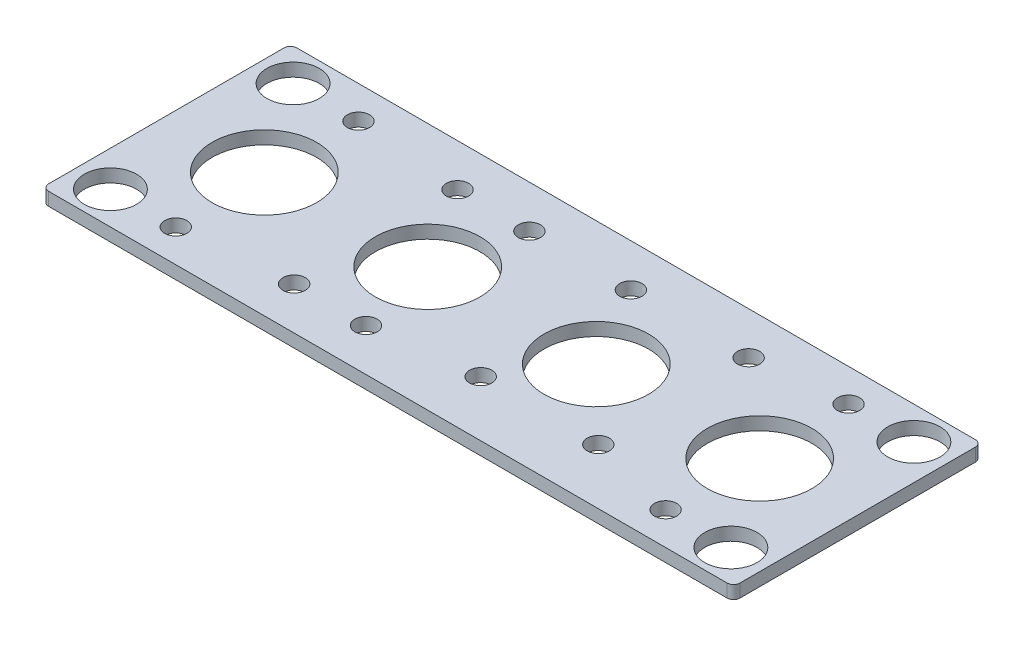
SolidWorks part; units mm, degrees
ref_plane "Front Plane" through (0, 0, 0) normal (0, 0, 1) x (1, 0, 0)
ref_plane "Top Plane" through (0, 0, 0) normal (0, 1, 0) x (1, 0, 0)
ref_plane "Right Plane" through (0, 0, 0) normal (1, 0, 0) x (0, 0, -1)
sketch "Sketch1" plane through (0, 0, 0) normal (0, 1, 0) x (1, 0, 0)
  line L1 (-52.9, 19) -> (52.9, 19)
  line L2 (-52.9, 19) -> (-52.9, -19)
  line L3 (-52.9, -19) -> (52.9, -19)
  line L4 (52.9, 19) -> (52.9, -19)
  circle A0 centre (-47.5, 14) radius 4
  circle A1 centre (-47.4521, -14) radius 4
  circle A2 centre (47.5, 14) radius 4
  circle A3 centre (47.5, -14) radius 4
  circle A4 centre (-20.8388, 12.5) radius 1.7
  circle A5 centre (-20.8388, -12.5) radius 1.7
  circle A6 centre (-9.8388, 12.5) radius 1.7
  circle A7 centre (-9.8388, -12.5) radius 1.7
  circle A8 centre (5.7083, 12.4823) radius 1.7
  circle A9 centre (5.7083, -10.5) radius 1.7
  circle A10 centre (23.7083, 12.5) radius 1.7
  circle A11 centre (23.7083, -10.5) radius 1.7
  circle A12 centre (-37.5, 14) radius 1.7
  circle A13 centre (-37.4521, -14) radius 1.7
  circle A14 centre (37.5, 14) radius 1.7
  circle A15 centre (37.5, -14) radius 1.7
  circle A16 centre (-37.9, 0) radius 8
  circle A17 centre (-12.9, 0) radius 8
  circle A19 centre (37.9, 0) radius 8
  circle A20 centre (12.9, 0) radius 8
  dimension "D3" = 28
  dimension "D4" = 95
  dimension "D5" = 105.8
  dimension "D7" = 11
  dimension "D10" = 6.5
  dimension "D13" = 10
  dimension "D18" = 75
  dimension "D19" = 52.9
  dimension "D25" = 15
  dimension "D24" = 15
  dimension "D26" = 25
  dimension "D1" = 5
  dimension "D2" = 5
  dimension "D6" = 5.4
  dimension "D8" = 25
  dimension "D9" = 6.5
  dimension "D11" = 23
  dimension "D12" = 18
  dimension "D14" = 10
  dimension "D15" = 10
  dimension "D16" = 10
  dimension "D17" = 28
  dimension "D20" = 19
  dimension "D21" = 0
  dimension "D22" = 25
  dimension "D23" = 11
  dimension "D27" = 25
extrude "Boss-Extrude3" add sketch "Sketch1" along normal blind 2
fillet "Fillet1" radius 1 4 edges at (52.9, 1, -19) (52.9, 1, 19) (-52.9, 1, -19) (-52.9, 1, 19)
